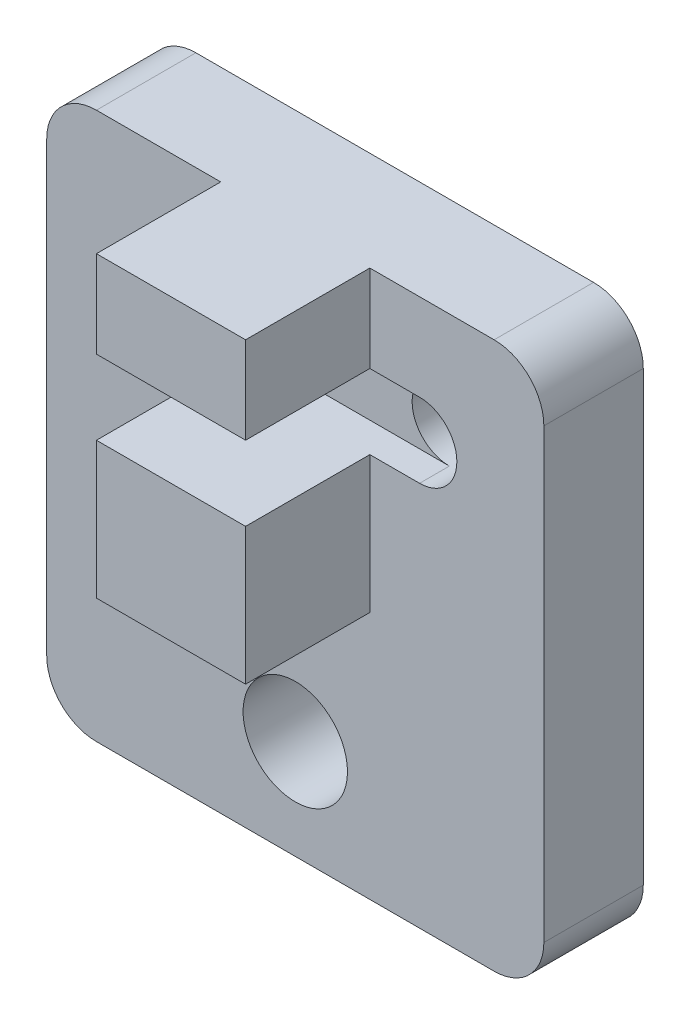
SolidWorks part; units mm, degrees
ref_plane "前视基准面" through (0, 0, 0) normal (0, 0, 1) x (1, 0, 0)
ref_plane "上视基准面" through (0, 0, 0) normal (0, 1, 0) x (1, 0, 0)
ref_plane "右视基准面" through (0, 0, 0) normal (1, 0, 0) x (0, 0, -1)
sketch "草图1" plane through (0, 0, 0) normal (0, 0, 1) x (1, 0, 0)
  line L0 (0, -1000) -> (0, 49000) construction
  line L1 (0, 0) -> (20, 0)
  line L2 (0, 0) -> (0, 22)
  line L3 (0, 22) -> (20, 22)
  line L4 (20, 0) -> (20, 22)
  line L5 (20, -987.7817) -> (20, 49012.2183) construction
  line L6 (-1000, 0) -> (49000, 0) construction
  line L7 (-980.4794, 40.6863) -> (49019.5206, 40.6863) construction
  line L8 (16, -954) -> (16, 49046) construction
  line L9 (20, 40.6863) -> (12, 40.6863) construction
  line L10 (20, 40.6863) -> (20, 46.6863) construction
  line L11 (20, 46.6863) -> (12, 46.6863) construction
  line L12 (12, 40.6863) -> (12, 46.6863) construction
  line L13 (10, -976) -> (10, 49024) construction
  line L14 (0, 22) -> (20, 22) construction
  line L15 (0, 22) -> (0, 10) construction
  line L16 (0, 10) -> (20, 10) construction
  line L17 (20, 22) -> (20, 10) construction
  line L19 (7, 22) -> (13, 22)
  line L20 (7, 22) -> (7, 10)
  line L21 (7, 10) -> (13, 10)
  line L22 (13, 22) -> (13, 10)
  circle A0 centre (10, 4) radius 2.1
  circle A1 centre (5, 17) radius 1.5
  circle A2 centre (15, 17) radius 1.5
  point P20 (16, 46.6863)
  point P27 (10, 22)
  dimension "D6" = 4.2
  dimension "D7" = 3
  dimension "D13" = 3
  dimension "D1" = 20
  dimension "D2" = 6
  dimension "D3" = 8
  dimension "D4" = 12
  dimension "D5" = 10
  dimension "D8" = 4
  dimension "D9" = 10
  dimension "D10" = 5
  dimension "D11" = 6
  dimension "D12" = 5
extrude "凸台-拉伸1" add sketch "草图1" along normal blind 4 contours L3 L22 L21 L20 L2 L1 L4 A0 A1 A2 region at (10, 9.977, 0)
extrude "凸台-拉伸2" add sketch "草图1<3>" along normal blind 9 contours L22 L3 L20 L21 region at (10, 16, 0)
sketch "草图1<3>" plane through (0, 0, 0) normal (0, 0, 1) x (1, 0, 0) same geometry as "草图1"
fillet "圆角1" radius 2 4 edges at (20, 0, 2) (0, 0, 2) (20, 22, 2) (0, 22, 2)
sketch "草图2" plane through (0, 0, 0) normal (-1, 0, 0) x (0, 0, 1)
  line L0 (4, 18.5) -> (0, 18.5) construction
  line L1 (2.8, 18.5) -> (4, 18.5)
  line L2 (2.8, 18.5) -> (2.8, 15.5)
  line L3 (2.8, 15.5) -> (4, 15.5)
  line L4 (4, 18.5) -> (4, 15.5) construction
  line L5 (4, 2) -> (4, 20) construction
  line L6 (4, 18.5) -> (14, 18.5)
  line L7 (14, 18.5) -> (14, 15.5)
  line L8 (14, 15.5) -> (4, 15.5)
  dimension "D1" = 3
  dimension "D2" = 1.2
  dimension "D3" = 10
extrude "切除-拉伸1" cut sketch "草图2" against normal blind 10 from offset 5 offset against normal yes
